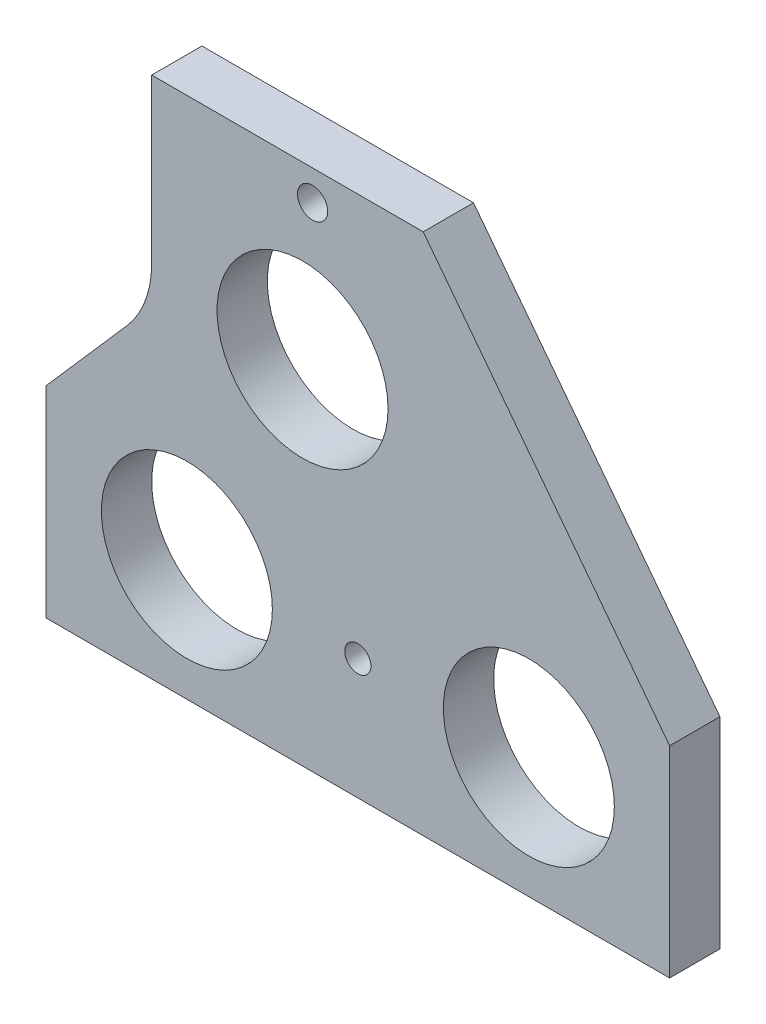
SolidWorks part; units mm, degrees
material "Stop 1060"
ref_plane "Płaszczyzna przednia" through (0, 0, 0) normal (0, 0, 1) x (1, 0, 0)
ref_plane "Płaszczyzna górna" through (0, 0, 0) normal (0, 1, 0) x (1, 0, 0)
ref_plane "Płaszczyzna prawa" through (0, 0, 0) normal (1, 0, 0) x (0, 0, -1)
sketch "Szkic1" plane through (0, 0, 0) normal (0, 0, 1) x (1, 0, 0)
  line L0 (-14, -12) -> (-14, 8)
  line L1 (-3.5, 40) -> (23.5, 40)
  line L2 (48, 8) -> (48, -12)
  line L3 (48, -12) -> (-14, -12)
  line L4 (-3.5, 40) -> (-3.5, 20)
  line L6 (-14, 8) -> (-3.5, 20)
  line L7 (23.5, 40) -> (48, 8)
  circle A0 centre (0, 0) radius 8.5
  circle A1 centre (34, 0) radius 8.5
  circle A2 centre (11.5, 23) radius 8.5
  circle A3 centre (12.5, 37) radius 1.5
  circle A4 centre (17, 0) radius 1.3
  dimension "D1" = 17
  dimension "D2" = 17
  dimension "D3" = 17
  dimension "D4" = 34
  dimension "D5" = 23
  dimension "D6" = 11.5
  dimension "D8" = 14
  dimension "D9" = 14
  dimension "D10" = 3
  dimension "D11" = 12
  dimension "D17" = 3
  dimension "D18" = 16
  dimension "D19" = 3
  dimension "D20" = 17
  dimension "D21" = 23
  dimension "3" = 2.6
  dimension "D7" = 12
  dimension "D12" = 20
  dimension "D13" = 27
  dimension "D14" = 20
  dimension "D15" = 20
  dimension "D16" = 24.5
extrude "Dodanie-wyciągnięcie1" add sketch "Szkic1" along normal blind 5
fillet "Zaokrąglenie1" radius 10 1 edges at (-3.5, 20, 2.5)
